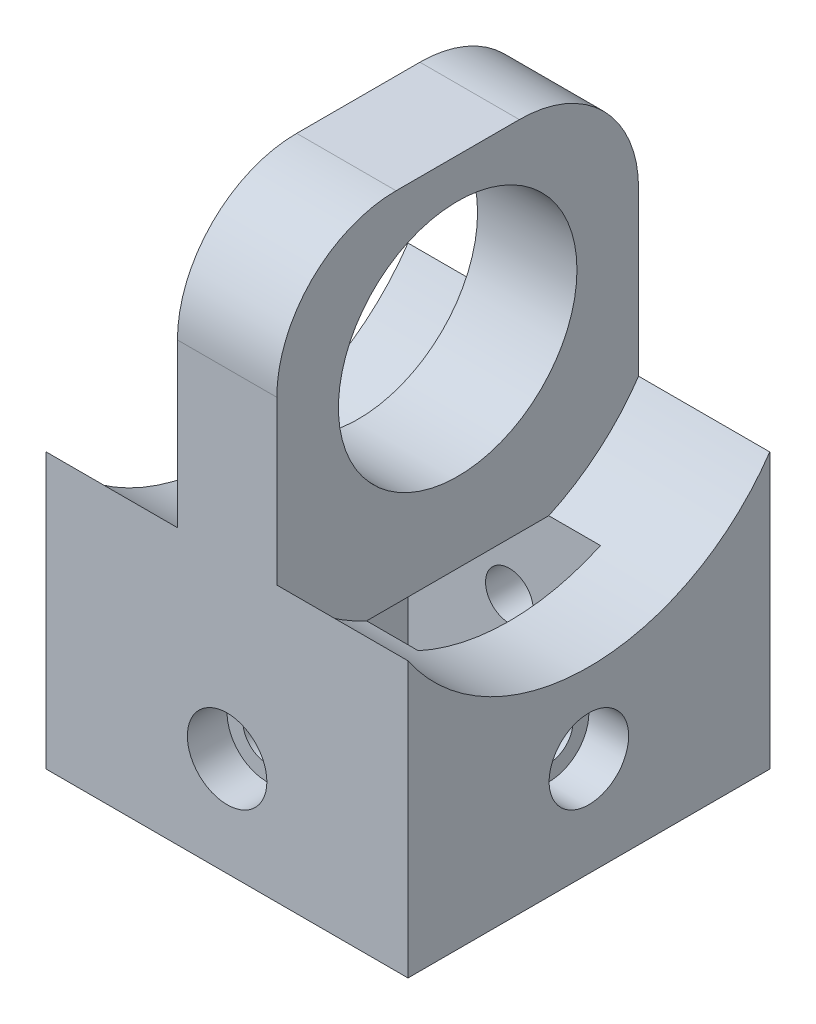
SolidWorks part; units mm, degrees
ref_plane "前视基准面" through (0, 0, 0) normal (0, 0, 1) x (1, 0, 0)
ref_plane "上视基准面" through (0, 0, 0) normal (0, 1, 0) x (1, 0, 0)
ref_plane "右视基准面" through (0, 0, 0) normal (1, 0, 0) x (0, 0, -1)
other "Configuration Table"
sketch "草图1" plane through (0, 0, 0) normal (0, 1, 0) x (1, 0, 0)
  line L13 (-2.55, -2.55) -> (2.55, -2.55)
  line L14 (-2.55, -2.55) -> (-2.55, 2.55)
  line L15 (-2.55, 2.55) -> (2.55, 2.55)
  line L16 (2.55, -2.55) -> (2.55, 2.55)
  line L17 (-2.55, -2.55) -> (2.55, 2.55) construction
  line L18 (-2.55, 2.55) -> (2.55, -2.55) construction
  line L19 (-4.55, 4.55) -> (4.55, 4.55)
  line L20 (-4.55, 4.55) -> (-4.55, -4.55)
  line L21 (-4.55, -4.55) -> (4.55, -4.55)
  line L22 (4.55, 4.55) -> (4.55, -4.55)
  dimension "D1" = 5.1
  dimension "D4" = 2
  dimension "D3" = 2
  dimension "D2" = 5.1
  dimension "D5" = 2
extrude "凸台-拉伸1" add sketch "草图1" along normal blind 5
sketch "草图2" plane through (0, 0, 4.55) normal (0, 0, 1) x (1, 0, 0)
  line L0 (-4.55, 5) -> (4.55, 5) construction
  circle A0 centre (0, 2.5) radius 0.6
  circle A1 centre (0, 2.5) radius 1
  dimension "D2" = 2
  dimension "D3" = 1.2
  dimension "D1" = 2.5
extrude "切除-拉伸1" cut sketch "草图2" against normal through all contours A0
extrude "切除-拉伸2" cut sketch "草图2<3>" against normal offset from surface (1 mm away) 1 contours A1 up to face at (-0.6, 2.5, 2.55)
sketch "草图2<3>" plane through (0, 0, 4.55) normal (0, 0, 1) x (1, 0, 0) same geometry as "草图2"
extrude "切除-拉伸3" cut sketch "草图2<4>" along normal offset from surface (1 mm away) 1 from surface contours A1 up to face at (0.6, 2.5, -2.55) starting at face at (0.6, 2.5, -4.55)
sketch "草图2<4>" plane through (0, 0, 4.55) normal (0, 0, 1) x (1, 0, 0) same geometry as "草图2"
sketch "草图3" plane through (-4.55, 0, 0) normal (-1, 0, 0) x (0, 0, 1)
  line L0 (-4.55, 5) -> (4.55, 5) construction
  circle A0 centre (0, 2.5) radius 1
  circle A1 centre (0, 2.5) radius 0.6
  dimension "D1" = 2
  dimension "D2" = 1.2
  dimension "D3" = 2.5
extrude "切除-拉伸4" cut sketch "草图3" against normal through all contours A1
extrude "切除-拉伸5" cut sketch "草图3<3>" against normal offset from surface (1 mm away) 1 contours A0 up to face at (-2.55, 2.5, -0.6)
sketch "草图3<3>" plane through (-4.55, 0, 0) normal (-1, 0, 0) x (0, 0, 1) same geometry as "草图3"
extrude "切除-拉伸6" cut sketch "草图3<4>" along normal offset from surface (1 mm away) 1 from surface contours A0 up to face at (2.55, 2.5, 0.6) starting at face at (4.55, 2.5, 0.6)
sketch "草图3<4>" plane through (-4.55, 0, 0) normal (-1, 0, 0) x (0, 0, 1) same geometry as "草图3"
sketch "草图5" plane through (0, 5, 0) normal (0, 1, 0) x (1, 0, 0)
  line L0 (-4.55, -4.55) -> (4.55, -4.55) construction
  line L1 (-1.25, -4.55) -> (1.25, -4.55)
  line L2 (-1.25, -4.55) -> (-1.25, 4.55)
  line L3 (-1.25, 4.55) -> (1.25, 4.55)
  line L4 (1.25, -4.55) -> (1.25, 4.55)
  line L5 (4.55, 4.55) -> (-4.55, 4.55) construction
  line L6 (4.55, -4.55) -> (4.55, 4.55) construction
  line L7 (-4.55, -4.55) -> (4.55, -4.55)
  line L8 (-4.55, -4.55) -> (-4.55, 4.55)
  line L9 (-4.55, 4.55) -> (4.55, 4.55)
  line L10 (4.55, -4.55) -> (4.55, 4.55)
  point P8 (0, -4.55)
  dimension "D1" = 2.5
extrude "凸台-拉伸2" add sketch "草图5" along normal blind 1 contours L10 L9 L8 L7
extrude "凸台-拉伸3" add sketch "草图5<4>" along normal blind 8 from surface contours L4 L3 L2 L1 starting at face at (0, 6, 0)
sketch "草图5<4>" plane through (0, 5, 0) normal (0, 1, 0) x (1, 0, 0) same geometry as "草图5"
sketch "草图6" plane through (1.25, 0, 0) normal (1, 0, 0) x (0, 0, -1)
  line L0 (-4.55, 14) -> (-4.55, 6) construction
  circle A0 centre (0, 10) radius 3
  point P4 (-4.55, 10)
  dimension "D1" = 6
extrude "切除-拉伸7" cut sketch "草图6" against normal through all contours A0
fillet "圆角1" radius 3 2 edges at (0, 14, 4.55) (0, 14, -4.55)
sketch "草图7" plane through (4.55, 0, 0) normal (1, 0, 0) x (0, 0, -1)
  line L0 (-4.55, 6.9101) -> (-4.55, 6)
  line L1 (-4.55, 11) -> (-4.55, 6) construction
  line L2 (-4.55, 6) -> (4.55, 6) construction
  line L3 (-4.55, 6) -> (-3.7749, 6)
  line L4 (4.55, 6.9101) -> (4.55, 6)
  line L5 (4.55, 11) -> (4.55, 6) construction
  line L6 (4.55, 6) -> (4.55, 0) construction
  line L7 (4.55, 6) -> (3.7749, 6)
  circle A0 centre (0, 10) radius 5.5
  line M5 (4.55, 6) -> (-4.55, 6)
  dimension "D1" = 11
  dimension "D2" = 10
extrude "切除-拉伸11" cut sketch "草图7" against normal up to surface (3.3 mm away) contours A0 M5 region at (4.55, 5.3924, 0) up to face at (1.25, 10, -3)
extrude "切除-拉伸12" cut sketch "草图7<2>" along normal up to surface (-5.8 mm away) from surface contours A0 M5 region at (4.55, 5.3924, 0) up to face at (-1.25, 10, -3) starting at face at (-4.55, 2.5, 1)
sketch "草图7<2>" plane through (4.55, 0, 0) normal (1, 0, 0) x (0, 0, -1) same geometry as "草图7"
extrude "凸台-拉伸4" add sketch "草图7<5>" against normal up to surface (3.3 mm away) contours A0 L0 M5 | A0 L4 M5 region at (4.55, 6.292, 4.3011) region at (4.55, 6.292, -4.3011) up to face at (1.25, 10, -3)
sketch "草图7<5>" plane through (4.55, 0, 0) normal (1, 0, 0) x (0, 0, -1) same geometry as "草图7"
extrude "凸台-拉伸5" add sketch "草图7<6>" along normal up to surface (-5.8 mm away) from surface contours A0 L0 M5 | A0 L4 M5 region at (4.55, 6.292, 4.3011) region at (4.55, 6.292, -4.3011) up to face at (-1.25, 10, -3) starting at face at (-4.55, 2.5, 1)
sketch "草图7<6>" plane through (4.55, 0, 0) normal (1, 0, 0) x (0, 0, -1) same geometry as "草图7"
